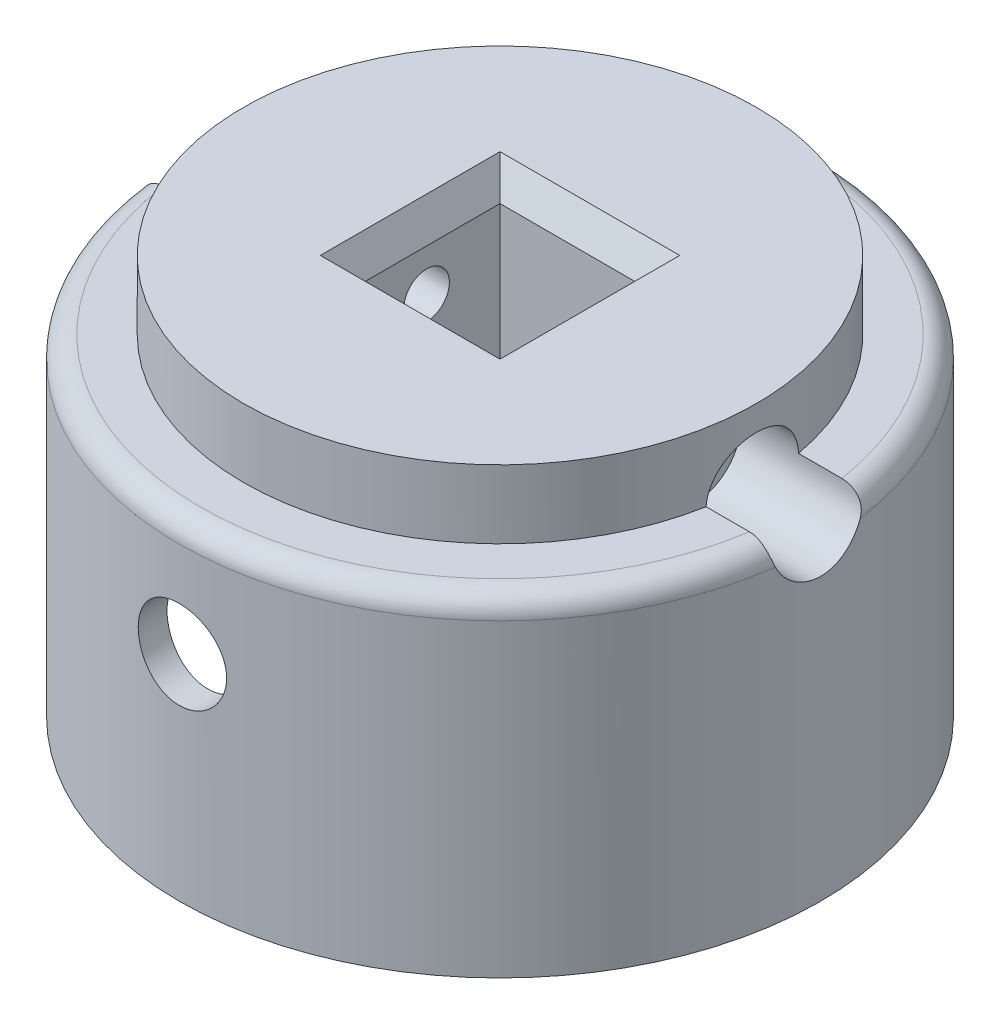
SolidWorks part; units mm, degrees
ref_plane "Спереди" through (0, 0, 0) normal (0, 0, 1) x (1, 0, 0)
ref_plane "Сверху" through (0, 0, 0) normal (0, 1, 0) x (1, 0, 0)
ref_plane "Справа" through (0, 0, 0) normal (1, 0, 0) x (0, 0, -1)
sketch "Sketch1" plane through (0, 0, 0) normal (0, 1, 0) x (1, 0, 0)
  circle A0 centre (0, 0) radius 22.5
  dimension "D1" = 45
extrude "Boss-Extrude1" add sketch "Sketch1" along normal blind 28
sketch "Sketch2" plane through (0, 0, 0) normal (0, -1, 0) x (1, 0, 0)
  line L1 (5.15, 5.15) -> (-5.15, 5.15)
  line L2 (5.15, 5.15) -> (5.15, -5.15)
  line L3 (5.15, -5.15) -> (-5.15, -5.15)
  line L4 (-5.15, 5.15) -> (-5.15, -5.15)
  line L5 (5.15, 5.15) -> (-5.15, -5.15) construction
  line L6 (5.15, -5.15) -> (-5.15, 5.15) construction
  point P0 (0, 0)
  dimension "D1" = 10.3
extrude "Cut-Extrude2" cut sketch "Sketch2" against normal through all
shell "Shell3" thickness 2 removed face at (0, 0, 0)
sketch "Sketch3" plane through (0, 0, 7.15) normal (0, 0, 1) x (1, 0, 0)
  line L0 (0, 26) -> (0, 0) construction
  line L1 (7.15, 26) -> (-7.15, 26) construction
  line L2 (7.15, 0) -> (-7.15, 0) construction
  line L3 (-22.5, 0) -> (22.5, 0) construction
  circle A0 centre (0, 15) radius 3.1
  dimension "D1" = 6.2
  dimension "D2" = 15
extrude "Cut-Extrude3" cut sketch "Sketch3" along normal through all
chamfer "Chamfer1" distance 2 angle 30 4 edges at (-5.15, 28, 0) (0, 28, 5.15) (5.15, 28, 0) (0, 28, -5.15) first distance on face at (-5.15, 14, 0) first distance on face at (0, 14, 5.15) first distance on face at (5.15, 14, 0) first distance on face at (0, 14, -5.15)
sketch "Sketch18" plane through (0, 26, 0) normal (0, -1, 0) x (1, 0, 0)
  line L0 (0, 0) -> (-18.4253, -8.9866) construction
  line L1 (0, 0) -> (-17.385, 10.8633) construction
  line L2 (0, 0) -> (0, -20.5) construction
  line L3 (-15.7289, -7.6715) -> (-18.4253, -8.9866)
  line L4 (-14.8408, 9.2736) -> (-17.385, 10.8633)
  circle A0 centre (0, 0) radius 20.5 construction
  arc A1 (-18.4253, -8.9866) -> (-17.385, 10.8633) centre (0, 0) cw
  arc A2 (-14.8408, 9.2736) -> (-15.7289, -7.6715) centre (0, 0) ccw
  dimension "D1" = 64
  dimension "D2" = 58
  dimension "D3" = 3
extrude "Boss-Extrude8" add sketch "Sketch18" along normal offset from surface (23 mm away) 3 up to face at (0, 0, 20.5)
sketch "Sketch9" plane through (0, 0, 0) normal (0, -1, 0) x (1, 0, 0)
  line L0 (0, -7.15) -> (0, -20.5) construction
  line L2 (2.0571, -22.4058) -> (-16.5967, -15.1921)
  line L3 (-16.5967, -15.1921) -> (-17.6788, -17.9902)
  line L4 (-17.6788, -17.9902) -> (0.975, -25.2038)
  line L5 (0.975, -25.2038) -> (2.0571, -22.4058)
  line L6 (-7.15, -7.15) -> (7.15, -7.15) construction
  line L7 (2.0571, -22.4058) -> (0, -7.15) construction
  circle A0 centre (0, 0) radius 22.5 construction
  circle A1 centre (0, 0) radius 20.5 construction
  dimension "D1" = 20
  dimension "D2" = 3
  dimension "D3" = 7.679
extrude "Boss-Extrude4" add sketch "Sketch9" against normal blind 20
sketch "Sketch11" plane through (0, 0, 0) normal (0, -1, 0) x (1, 0, 0)
  line L0 (2.0571, -22.4058) -> (7.15, -7.15)
  line L1 (7.15, -7.15) -> (-7.15, -7.15)
  line L2 (-7.15, -7.15) -> (-16.5967, -15.1921)
  line L3 (-16.5967, -15.1921) -> (2.0571, -22.4058) construction
  line L4 (-3.78, -20.1485) -> (-10.7596, -17.4494) construction
  arc A0 (2.0571, -22.4058) -> (-16.5967, -15.1921) centre (0, 0) ccw construction
  arc A1 (2.0571, -22.4058) -> (-16.5967, -15.1921) centre (0, 0) cw
  arc A2 (2.0571, -22.4058) -> (-16.5967, -15.1921) centre (0, 0) ccw construction
  point P4 (-7.2698, -18.7989)
extrude "Boss-Extrude6" add sketch "Sketch11" against normal up to surface (26 mm away) up to face at (0, 26, 0)
sketch "Sketch12" plane through (0, 0, 0) normal (0, -1, 0) x (1, 0, 0)
  line L0 (-7.15, -7.15) -> (-15.0727, -13.8947) construction
  line L1 (2.7554, -20.314) -> (7.15, -7.15) construction
  line L2 (3.8359, -17.0772) -> (2.7554, -20.314)
  line L3 (-15.0727, -13.8947) -> (-12.7884, -11.95)
  arc A0 (2.7554, -20.314) -> (-15.0727, -13.8947) centre (0, 0) cw
  arc A1 (-12.7884, -11.95) -> (3.8359, -17.0772) centre (0, 0) ccw
  arc A2 (2.7554, -20.314) -> (-15.0727, -13.8947) centre (0, 0) ccw construction
  dimension "D1" = 3
extrude "Cut-Extrude5" cut sketch "Sketch12" against normal blind 12
sketch "Sketch17" plane through (0, 0, 0) normal (0, -1, 0) x (1, 0, 0)
  line L0 (7.15, 7.15) -> (7.15, -7.15)
  line L1 (7.15, -7.15) -> (3.8359, -17.0772)
  line L2 (7.15, 7.15) -> (-7.15, 7.15)
  line L3 (-7.15, 7.15) -> (-7.15, -7.15)
  line L4 (-7.15, -7.15) -> (-12.7884, -11.95)
  arc A0 (3.8359, -17.0772) -> (-12.7884, -11.95) centre (0, 0) cw
  arc A1 (-12.7884, -11.95) -> (3.8359, -17.0772) centre (0, 0) ccw construction
extrude "Cut-Extrude9" cut sketch "Sketch17" against normal blind 2
sketch "Sketch20" plane through (0, 26, 0) normal (0, -1, 0) x (1, 0, 0)
  line L0 (2.7554, -20.314) -> (7.15, -7.15)
  line L1 (7.15, -7.15) -> (7.15, 7.15)
  line L2 (7.15, 7.15) -> (-7.15, 7.15)
  line L3 (-7.15, 7.15) -> (-7.15, -7.15)
  line L4 (-7.15, -7.15) -> (-15.0727, -13.8947)
  arc A0 (2.7554, -20.314) -> (-15.0727, -13.8947) centre (0, 0) ccw
  arc A1 (2.7554, -20.314) -> (-17.385, 10.8633) centre (0, 0) ccw construction
extrude "Boss-Extrude10" add sketch "Sketch20" along normal blind 7
sketch "Sketch21" plane through (0, 28, 0) normal (0, 1, 0) x (1, 0, 0)
  circle A0 centre (0, 0) radius 18
  dimension "D1" = 36
extrude "Cut-Extrude11" cut sketch "Sketch21" against normal blind 4.8 flip side to cut
sketch "Sketch22" plane through (5.15, 0, 0) normal (-1, 0, 0) x (0, 0, 1)
  line L0 (0, 26) -> (0, 2) construction
  line L1 (5.15, 26) -> (-5.15, 26) construction
  line L2 (-5.15, 2) -> (5.15, 2) construction
  line L3 (-6.3047, 28) -> (6.3047, 28) construction
  circle A0 centre (0, 23) radius 1.6
  point P10 (0, 28)
  dimension "D1" = 3.2
  dimension "D2" = 5
extrude "Cut-Extrude12" cut sketch "Sketch22" against normal through all both and the other way through all
sketch "Sketch24" plane through (5.15, 0, 0) normal (-1, 0, 0) x (0, 0, 1)
  circle A0 centre (0, 23) radius 3.25
  dimension "D1" = 6.5
extrude "Cut-Extrude13" cut sketch "Sketch24" against normal through all from offset 8.5 offset against normal yes
sketch "Sketch25" plane through (-5.15, 0, 0) normal (1, 0, 0) x (0, 0, -1)
  line L0 (-5.15, 26) -> (-5.15, 2) construction
  line L1 (0, 19.75) -> (2.8146, 21.375)
  line L2 (2.8146, 21.375) -> (2.8146, 24.625)
  line L3 (2.8146, 24.625) -> (0, 26.25)
  line L4 (0, 26.25) -> (-2.8146, 24.625)
  line L5 (-2.8146, 24.625) -> (-2.8146, 21.375)
  line L6 (-2.8146, 21.375) -> (0, 19.75)
  circle A0 centre (0, 23) radius 3.25 construction
  dimension "D1" = 6.5
extrude "Cut-Extrude14" cut sketch "Sketch25" against normal through all from offset 8.5 offset against normal yes
fillet "Fillet1" radius 1.5 2 edges at (-0.2166, 23.2, 22.499) (-0.2166, 23.2, -22.499)
sketch "Sketch26" plane through (0, 0, 0) normal (0, -1, 0) x (1, 0, 0)
  circle A0 centre (0, 0) radius 22.5
  arc A1 (2.0571, -22.4058) -> (-16.5967, -15.1921) centre (0, 0) ccw construction
  circle A2 centre (0, 0) radius 43.9199
extrude "Cut-Extrude15" cut sketch "Sketch26" against normal through all
